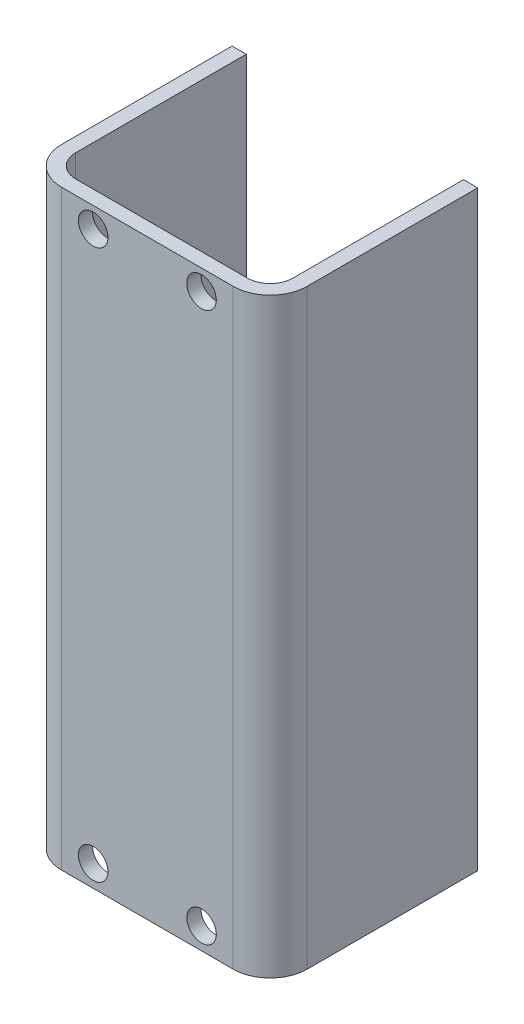
SolidWorks part; units mm, degrees
ref_plane "Front Plane" through (0, 0, 0) normal (0, 0, 1) x (1, 0, 0)
ref_plane "Top Plane" through (0, 0, 0) normal (0, 1, 0) x (1, 0, 0)
ref_plane "Right Plane" through (0, 0, 0) normal (1, 0, 0) x (0, 0, -1)
sketch "Sketch1" plane through (0, 0, 0) normal (0, 1, 0) x (1, 0, 0)
  line L0 (4, 0) -> (34.2, 0)
  line L1 (38.2, 4) -> (38.2, 34)
  line L2 (0, 4) -> (0, 34)
  line L3 (-2.5, 4) -> (-2.5, 34)
  line L4 (4, -2.5) -> (34.2, -2.5)
  line L5 (40.7, 4) -> (40.7, 34)
  line L6 (-2.5, 34) -> (0, 34)
  line L7 (38.2, 34) -> (40.7, 34)
  arc A0 (34.2, 0) -> (38.2, 4) centre (34.2, 4) ccw
  arc A1 (4, 0) -> (0, 4) centre (4, 4) cw
  arc A2 (4, -2.5) -> (-2.5, 4) centre (4, 4) cw
  arc A3 (34.2, -2.5) -> (40.7, 4) centre (34.2, 4) ccw
  point P7 (38.2, 0)
  point P10 (0, 0)
  dimension "D4" = 4
  dimension "D1" = 38.2
  dimension "D2" = 34
  dimension "D3" = 34
  dimension "D5" = 2.5
extrude "Boss-Extrude1" add sketch "Sketch1" along normal blind 104
sketch "Sketch2" plane through (0, 0, 2.5) normal (0, 0, 1) x (1, 0, 0)
  line L0 (4, 0) -> (34.2, 0) construction
  circle A0 centre (9.575, 3.81) radius 2.6
  circle A1 centre (28.625, 3.81) radius 2.6
  circle A2 centre (9.575, 100.41) radius 2.6
  circle A3 centre (28.625, 100.41) radius 2.6
  point P6 (19.1, 0)
  dimension "D2" = 5.2
  dimension "D5" = 5.2
  dimension "D1" = 3.81
  dimension "D3" = 9.525
  dimension "D4" = 9.525
  dimension "D6" = 3.81
  dimension "D7" = 2
extrude "Cut-Extrude1" cut sketch "Sketch2" against normal blind 108
sketch "Sketch3" plane through (0, 0, 0) normal (0, 0, -1) x (-1, 0, 0)
  line L0 (-34.2, 104) -> (-34.2, 0) construction
  line L1 (-34.2, 49.5953) -> (-4, 49.5953)
  line L2 (-34.2, 49.5953) -> (-34.2, 55.5953)
  line L3 (-34.2, 55.5953) -> (-4, 55.5953)
  line L4 (-4, 49.5953) -> (-4, 55.5953)
  line L5 (-4, 104) -> (-4, 0) construction
  point P8 (-34.2, 52.5953)
  dimension "D1" = 3
extrude "Boss-Extrude2" add sketch "Sketch3" along normal blind 2
chamfer "Chamfer1" distance 10 distance2 2 2 edges at (34.2, 52.5953, 0) (4, 52.5953, 0) first distance on face at (35.8095, 52.1984, -1.0572) first distance on face at (2.3905, 52.1984, -1.0572)
fillet "Fillet1" radius 3 2 edges at (37.2339, 52.5953, -1.3932) (0.9661, 52.5953, -1.3932)
